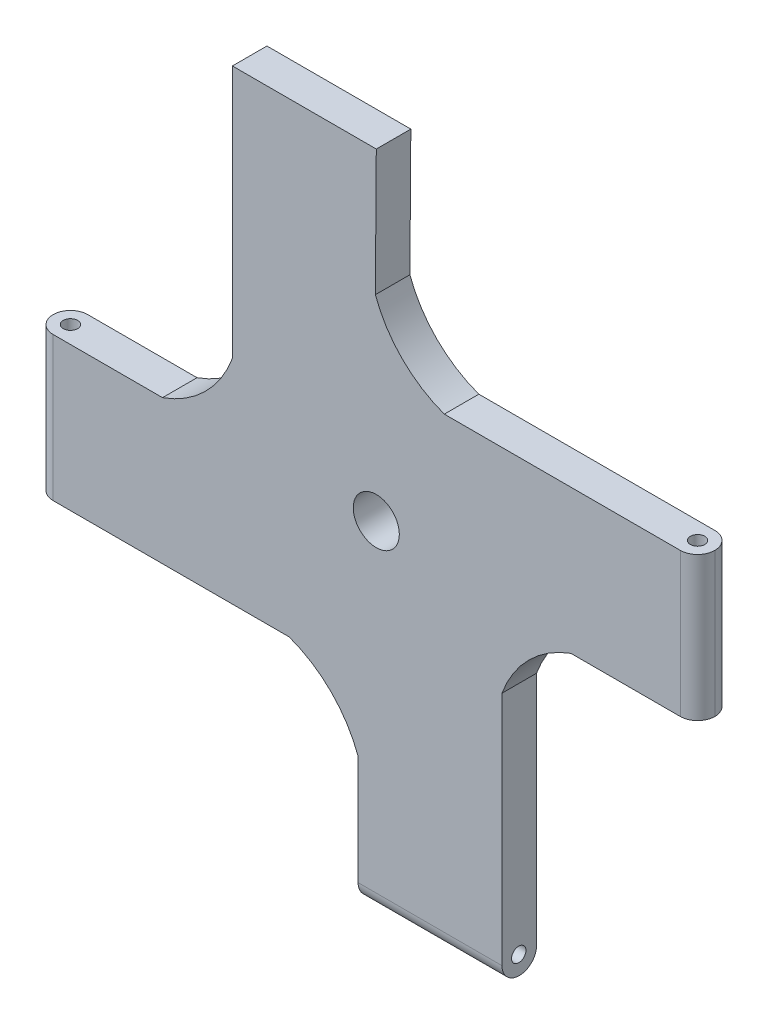
SolidWorks part; units mm, degrees
ref_plane "정면" through (0, 0, 0) normal (0, 0, 1) x (1, 0, 0)
ref_plane "윗면" through (0, 0, 0) normal (0, 1, 0) x (1, 0, 0)
ref_plane "우측면" through (0, 0, 0) normal (1, 0, 0) x (0, 0, -1)
sketch "스케치2" plane through (0, 0, 0) normal (0, 0, 1) x (1, 0, 0)
  line L0 (-102.5253, -57.6011) -> (-102.5253, -32.6011)
  line L1 (-68.3848, 23.378) -> (-43.3848, 23.378)
  line L2 (-68.3848, 23.378) -> (-68.3848, -20.622)
  line L3 (-46.5456, -91.5809) -> (-21.5456, -91.5809)
  line L4 (12.4342, -35.6011) -> (-9.5658, -35.6011)
  line L5 (12.4342, -35.6011) -> (12.4342, -10.6011)
  line L6 (-43.3848, 23.378) -> (-43.5456, 1.3786)
  line L7 (-102.5253, -57.6011) -> (-58.5253, -57.6011)
  line L8 (12.4342, -10.6011) -> (-31.5658, -10.6011)
  line L9 (-21.5456, -91.5809) -> (-21.5456, -47.5809)
  line L10 (-46.5456, -91.5809) -> (-46.5456, -69.5809)
  line L11 (-102.5253, -32.6011) -> (-80.5253, -32.6011)
  line L12 (-43.3848, 23.378) -> (-43.3848, -91.5809) construction
  line L14 (-102.5253, -32.6011) -> (12.4342, -32.6011) construction
  circle A0 centre (-43.3848, -32.6011) radius 4
  arc A2 (-31.5658, -10.6011) -> (-43.5456, 1.3786) centre (-24.7447, 8.1997) cw
  arc A3 (-9.5658, -35.6011) -> (-21.5456, -47.5809) centre (-2.7447, -54.402) ccw
  arc A4 (-58.5253, -57.6011) -> (-46.5456, -69.5809) centre (-65.3464, -76.402) cw
  arc A5 (-80.5253, -32.6011) -> (-68.3848, -20.622) centre (-87.1613, -13.7342) ccw
  point P0 (-43.3848, -32.6011)
  dimension "D3" = 25
  dimension "D4" = 22
  dimension "D8" = 20
  dimension "D10" = 20
  dimension "D12" = 20
  dimension "D16" = 59.1405
  dimension "D1" = 25
  dimension "D2" = 25
  dimension "D5" = 44
  dimension "D6" = 22
  dimension "D7" = 22
  dimension "D9" = 44
  dimension "D11" = 44
  dimension "D13" = 44
  dimension "D14" = 25
  dimension "D15" = 22
extrude "보스-돌출1" add sketch "스케치2" along normal blind 6 contours A5 L11 L0 L7 A4 L10 L3 L9 A3 L4 L5 L8 A2 L6 L1 L2 region at (-100.8995, -45.1011, 0)
ref_plane "평면1" through (0, -57.6011, 0) normal (0, -1, 0) x (-1, 0, 0)
sketch "스케치3" plane through (0, -57.6011, 0) normal (0, -1, 0) x (-1, 0, 0)
  line L0 (102.5253, -3) -> (43.3853, -3) construction
  line L3 (102.5253, -6) -> (102.5253, 0) construction
  circle A0 centre (99.5253, -3) radius 1.25
  point P4 (99.5253, -3)
  dimension "D3" = 2.5
  dimension "D1" = 59.14
  dimension "D2" = 56.14
extrude "컷-돌출1" cut sketch "스케치3" against normal blind 5
ref_plane "평면2" through (0, -32.6011, 0) normal (0, 1, 0) x (1, 0, 0)
sketch "스케치4" plane through (0, -32.6011, 0) normal (0, 1, 0) x (1, 0, 0)
  circle A0 centre (-99.5253, -3) radius 1.25
  dimension "D1" = 2.5
extrude "컷-돌출2" cut sketch "스케치4" against normal blind 5
ref_plane "평면3" through (-21.5456, 0, 0) normal (1, 0, 0) x (0, 0, -1)
sketch "스케치5" plane through (-21.5456, 0, 0) normal (1, 0, 0) x (0, 0, -1)
  line L1 (-3.0876, -91.3478) -> (-3.0876, -32.2078) construction
  circle A1 centre (-3.0876, -88.3478) radius 1.25
  point P7 (-3.0876, -88.3478)
  dimension "D3" = 59.14
  dimension "D4" = 56.14
extrude "컷-돌출3" cut sketch "스케치5" against normal blind 5
ref_plane "평면4" through (-46.5456, 0, 0) normal (-1, 0, 0) x (0, 0, 1)
sketch "스케치6" plane through (-46.5456, 0, 0) normal (-1, 0, 0) x (0, 0, 1)
  circle A0 centre (3.0876, -88.3478) radius 1.25
extrude "컷-돌출4" cut sketch "스케치6" against normal blind 5
ref_plane "평면5" through (0, -10.6011, 0) normal (0, 1, 0) x (1, 0, 0)
sketch "스케치8" plane through (0, -10.6011, 0) normal (0, 1, 0) x (1, 0, 0)
  line L1 (12.4342, -3) -> (-46.7058, -3) construction
  line L2 (12.4342, -6) -> (12.4342, 0) construction
  circle A1 centre (9.4342, -3) radius 1.25
  point P9 (9.4342, -3)
  dimension "D3" = 59.14
  dimension "D4" = 56.14
extrude "컷-돌출5" cut sketch "스케치8" against normal blind 5
ref_plane "평면6" through (0, -35.6011, 0) normal (0, -1, 0) x (-1, 0, 0)
sketch "스케치9" plane through (0, -35.6011, 0) normal (0, -1, 0) x (-1, 0, 0)
  circle A0 centre (-9.4342, -3) radius 1.25
extrude "컷-돌출6" cut sketch "스케치9" against normal blind 5
fillet "필렛2" radius 3 6 edges at (12.4342, -23.1011, 0) (12.4342, -23.1011, 6) (-34.0456, -91.5809, 0) (-34.0456, -91.5809, 6) (-102.5253, -45.1011, 0) (-102.5253, -45.1011, 6)
